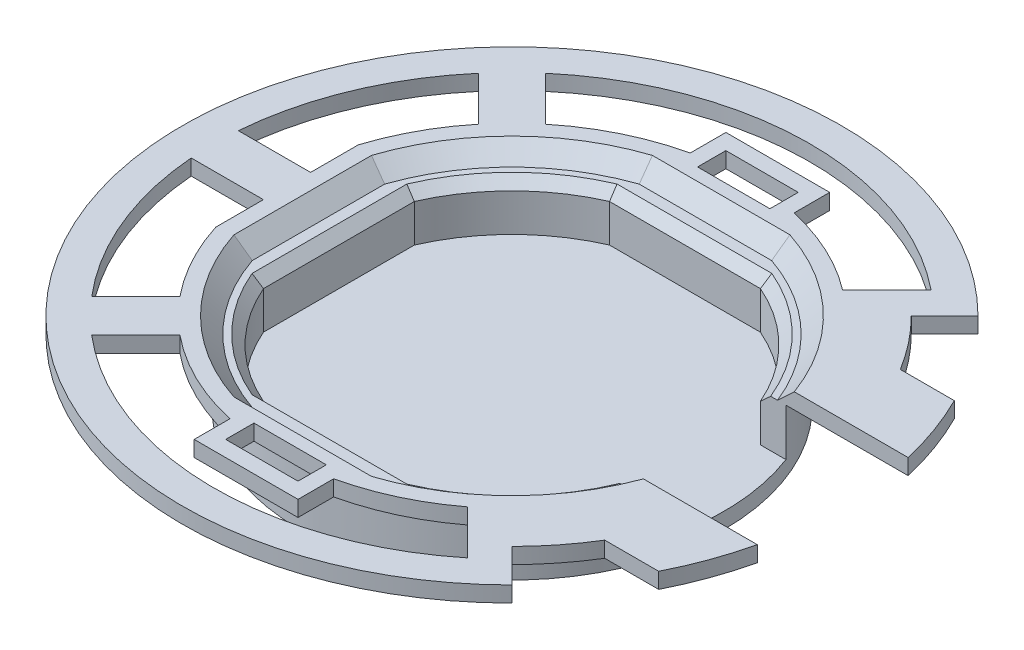
SolidWorks part; units mm, degrees
ref_plane "Front Plane" through (0, 0, 0) normal (0, 0, 1) x (1, 0, 0)
ref_plane "Top Plane" through (0, 0, 0) normal (0, 1, 0) x (1, 0, 0)
ref_plane "Right Plane" through (0, 0, 0) normal (1, 0, 0) x (0, 0, -1)
sketch "Front" plane through (0, 0, 0) normal (0, 0, 1) x (1, 0, 0)
  line L0 (0, 0) -> (0, 4407.3663) construction
  line L1 (0, 0) -> (4407.3663, 0) construction
  line L2 (0, 2.5) -> (-20.95, 2.5)
  line L3 (-20.95, 2.5) -> (-20.95, 1.5)
  line L4 (-20.95, 1.5) -> (-13.5, 1.5)
  line L5 (-13.5, 1.5) -> (-13.5, -2.5)
  line L6 (-13.5, -2.5) -> (0, -2.5)
  line L7 (0, -2.5) -> (0, 2.5)
  dimension "D1" = 1
  dimension "D2" = 41.9
  dimension "D3" = 5
  dimension "D4" = 27
sketch "Top" plane through (0, 0, 0) normal (0, 1, 0) x (1, 0, 0)
  line L0 (0, 0) -> (0, 50000) construction
  line L1 (0, 0) -> (50000, 0) construction
sketch "Right" plane through (0, 0, 0) normal (1, 0, 0) x (0, 0, -1)
  line L0 (0, 0) -> (0, 50000) construction
  line L1 (0, 0) -> (50000, 0) construction
revolve "Base" add sketch "Front" angle 360 about L0
sketch "Sketch2" plane through (0, 2.5, 0) normal (0, 1, 0) x (1, 0, 0)
  line L0 (0, 0) -> (50000, 0) construction
  line L1 (0, 0) -> (0, 50000) construction
  line L2 (-4.2083, 12.3) -> (4.2083, 12.3)
  line L3 (-12.3, -4.2083) -> (-12.3, 4.2083)
  line L4 (-4.2083, -12.3) -> (4.2083, -12.3)
  line L5 (12.3, -4.2083) -> (12.3, 4.2083)
  line L6 (-2.3, -14.1) -> (2.3, -14.1)
  line L7 (-2.3, 15.9) -> (2.3, 15.9)
  line L8 (-2.3, 15.9) -> (-2.3, 14.1)
  line L9 (-2.3, 14.1) -> (2.3, 14.1)
  line L10 (2.3, 15.9) -> (2.3, 14.1)
  line L11 (-2.3, 15.9) -> (2.3, 14.1) construction
  line L12 (-2.3, 14.1) -> (2.3, 15.9) construction
  line L13 (2.3, -15.9) -> (2.3, -14.1)
  line L14 (-2.3, -15.9) -> (2.3, -15.9)
  line L15 (-2.3, -15.9) -> (-2.3, -14.1)
  line L16 (-2.3, -14.1) -> (2.3, -15.9) construction
  line L17 (-2.3, -15.9) -> (2.3, -14.1) construction
  circle A0 centre (0, 0) radius 13 construction
  arc A1 (-12.3, 4.2083) -> (-4.2083, 12.3) centre (0, 0) cw
  arc A2 (-12.3, -4.2083) -> (-4.2083, -12.3) centre (0, 0) ccw
  arc A3 (12.3, -4.2083) -> (4.2083, -12.3) centre (0, 0) cw
  arc A4 (12.3, 4.2083) -> (4.2083, 12.3) centre (0, 0) ccw
  point P7 (0, 15)
  point P15 (-12.3, 0)
  point P16 (0, -12.3)
  point P19 (0, 12.3)
  point P28 (0, -15)
  dimension "D1" = 26
  dimension "D2" = 24.6
  dimension "D3" = 1.8
  dimension "D4" = 4.6
  dimension "D5" = 30
extrude "Watch Positioner" cut sketch "Sketch2" against normal up to surface (1 mm away) contours L5 A4 L2 A1 L3 A2 L4 A3 | L10 L7 L8 L9 | L15 L14 L13 L6 up to face at (0, 1.5, -13.5)
sketch "Sketch4" plane through (0, 2.5, 0) normal (0, 1, 0) x (1, 0, 0)
  line L1 (4.7958, 12.6194) -> (-4.7958, 12.6194) construction
  line L2 (-4.7958, 11) -> (-4.7958, 12.6194) construction
  line L3 (4.7958, -11) -> (-4.7958, -11)
  line L4 (11, 4.7958) -> (11, -4.7958) construction
  line L5 (11, 4.7958) -> (21.95, 4.7958)
  line L6 (21.95, 4.7958) -> (21.95, -4.7958)
  line L7 (0, 0) -> (50000, 0) construction
  line L8 (0, 7.5051) -> (0, 50007.5051) construction
  line L9 (11, -4.7958) -> (21.95, -4.7958)
  line L10 (15.2945, 9.3958) -> (19.8374, 9.3958)
  line L12 (15.521, 15.521) -> (12.6926, 12.6926)
  line L13 (15.521, -15.521) -> (12.6926, -12.6926)
  line L14 (15.2945, -9.3958) -> (19.8374, -9.3958)
  line L15 (-11, 4.7958) -> (-11, -4.7958)
  line L18 (4.7958, 11) -> (-4.7958, 11)
  circle A0 centre (0, 0) radius 12 construction
  arc A1 (-4.7958, -11) -> (-11, -4.7958) centre (0, 0) cw
  arc A2 (4.7958, -11) -> (11, -4.7958) centre (0, 0) ccw
  arc A3 (4.7958, 11) -> (11, 4.7958) centre (0, 0) cw
  arc A4 (15.521, 15.521) -> (19.8374, 9.3958) centre (0, 0) cw
  arc A5 (12.6926, -12.6926) -> (15.2945, -9.3958) centre (0, 0) ccw
  arc A6 (15.521, -15.521) -> (19.8374, -9.3958) centre (0, 0) ccw
  circle A7 centre (0, 0) radius 21.95
  circle A8 centre (0, 0) radius 21.95 construction
  arc A9 (12.6926, 12.6926) -> (15.2945, 9.3958) centre (0, 0) cw
  circle A10 centre (0, 0) radius 17.95
  circle A11 centre (0, 0) radius 17.95 construction
  circle A12 centre (0, 0) radius 13.5 construction
  arc A18 (-4.7958, 11) -> (-11, 4.7958) centre (0, 0) ccw
  point P13 (-11, 0)
  point P16 (0, -11)
  point P19 (0, 11)
  point P28 (21.95, 0)
  dimension "D1" = 24
  dimension "D5" = 45
  dimension "D7" = 1.5
  dimension "D2" = 22
  dimension "D3" = 1
  dimension "D6" = 4.6
  dimension "D4" = 3
extrude "Watch Holder v2" cut sketch "Sketch4" against normal offset from surface (4 mm away) 1 up to face at (0, -2.5, -13.5)
chamfer "Chamfer1" distance 0.6 angle 45 7 edges at (8.4853, 1.5, 8.4853) (0, 1.5, 11) (-8.4853, 1.5, 8.4853) (-11, 1.5, 0) (-8.4853, 1.5, -8.4853) (0, 1.5, -11) (8.4853, 1.5, -8.4853)
sketch "Sketch5" plane through (0, 0, 0) normal (0, 1, 0) x (1, 0, 0)
  line L1 (0, 0) -> (50000, 0) construction
  line L2 (0, 0) -> (0, 50000) construction
  line L7 (0, 0) -> (35355.3391, -35355.3391) construction
  line L8 (-0.7117, -0.7117) -> (35354.6274, 35354.6274) construction
  line L10 (-12.297, 14.4183) -> (-9.4928, 11.6141)
  line L18 (-14.4183, 12.297) -> (-11.6141, 9.4928)
  line L19 (-18.8905, 1.5) -> (-14.3, 1.5)
  line L21 (-18.8905, -1.5) -> (-14.3, -1.5)
  line L22 (-14.4183, -12.297) -> (-11.6141, -9.4928)
  line L23 (-14.3, -1.5) -> (-14.3, -4.5288)
  line L24 (9.0977, -11.9261) -> (11.9106, -14.739)
  line L25 (3.3, -14.6325) -> (3.3, -16.9)
  line L26 (-3.3, 16.9) -> (-3.3, 13.1)
  line L44 (3.3, -16.9) -> (-3.3, -16.9)
  line L45 (-3.3, 13.1) -> (3.3, 13.1)
  line L46 (3.3, 13.1) -> (3.3, 16.9)
  line L47 (3.3, 16.9) -> (-3.3, 16.9)
  line L48 (-3.3, 16.9) -> (-3.3, 14.6325)
  line L50 (3.3, 14.6325) -> (3.3, 16.9)
  line L51 (3.3, 16.9) -> (-3.3, 16.9)
  line L52 (-3.3, -16.9) -> (-3.3, -14.6325)
  line L53 (-12.297, -14.4183) -> (-9.4928, -11.6141)
  line L70 (17.4472, 7.3958) -> (14.1317, 7.3958)
  line L71 (13.3722, 6.7958) -> (17.6895, 6.7958)
  line L72 (-14.3, -4.2083) -> (-14.3, 4.5288)
  line L73 (-4.5288, 14.3) -> (4.5288, 14.3)
  line L74 (9.7751, 12.6036) -> (11.9106, 14.739)
  line L77 (-14.3, 1.5) -> (-14.3, 4.5288)
  line L79 (9.0977, 11.9261) -> (11.9106, 14.739)
  arc A11 (-11.6141, 9.4928) -> (-14.3, 4.5288) centre (0, 0) ccw
  arc A12 (-14.4183, 12.297) -> (-18.8905, 1.5) centre (0, 0) ccw
  arc A13 (-14.4183, -12.297) -> (-18.8905, -1.5) centre (0, 0) cw
  arc A14 (-11.6141, -9.4928) -> (-14.3, -4.5288) centre (0, 0) cw
  arc A15 (11.9106, -14.739) -> (-12.297, -14.4183) centre (0, 0) cw
  arc A16 (9.0977, -11.9261) -> (3.3, -14.6325) centre (0, 0) cw
  arc A17 (-3.3, -14.6325) -> (-9.4928, -11.6141) centre (0, 0) cw
  arc A55 (14.1317, 7.3958) -> (9.7751, 12.6036) centre (0, 0) ccw
  arc A56 (17.6895, 6.7958) -> (17.4472, 7.3958) centre (0, 0) ccw
  arc A57 (-4.5288, 14.3) -> (-14.3, 4.5288) centre (0, 0) ccw
  arc A58 (13.3722, 6.7958) -> (4.5288, 14.3) centre (0, 0) ccw
  arc A59 (11.9106, 14.739) -> (13.3997, -13.3997) centre (0, 0) ccw
  arc A62 (-3.3, 14.6325) -> (-9.4928, 11.6141) centre (0, 0) ccw
  arc A63 (9.0977, 11.9261) -> (3.3, 14.6325) centre (0, 0) ccw
  arc A64 (11.9106, 14.739) -> (-12.297, 14.4183) centre (0, 0) ccw
  dimension "D3" = 45
  dimension "D2" = 1
  dimension "D4" = 3
  dimension "D5" = 3
  dimension "D1" = 2
extrude "Cut-Extrude1" cut sketch "Sketch5" along normal through all both and the other way through all
chamfer "Chamfer2" distance 1 angle 45 7 edges at (8.9683, 2.5, 9.4111) (0, 2.5, 12.3) (-9.1924, 2.5, 9.1924) (-12.3, 2.5, 0) (-9.1924, 2.5, -9.1924) (0, 2.5, -12.3) (8.9683, 2.5, -9.4111)
